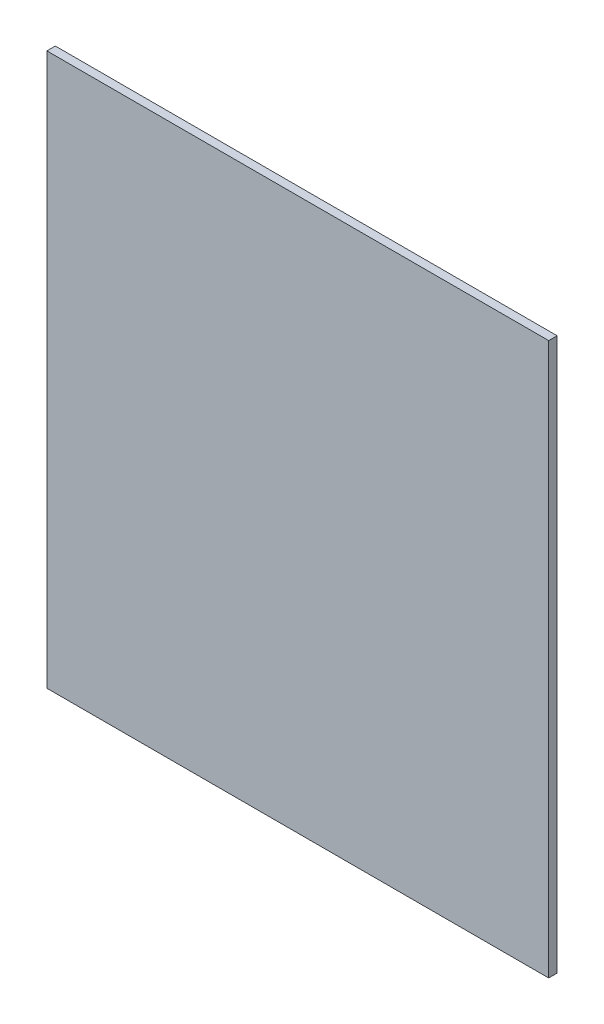
SolidWorks part; units mm, degrees
ref_plane "Plan de face" through (0, 0, 0) normal (0, 0, 1) x (1, 0, 0)
ref_plane "Plan de dessus" through (0, 0, 0) normal (0, 1, 0) x (1, 0, 0)
ref_plane "Plan de droite" through (0, 0, 0) normal (1, 0, 0) x (0, 0, -1)
sketch "Sketch1" plane through (0, 0, 0) normal (0, 0, 1) x (1, 0, 0)
  line L1 (-220.2282, 110.1141) -> (29.7718, 110.1141)
  line L2 (-220.2282, 110.1141) -> (-220.2282, -164.8859)
  line L3 (-220.2282, -164.8859) -> (29.7718, -164.8859)
  line L4 (29.7718, 110.1141) -> (29.7718, -164.8859)
  dimension "D1" = 275
  dimension "D2" = 250
extrude "Boss-Extrude1" add sketch "Sketch1" along normal blind 4.2
